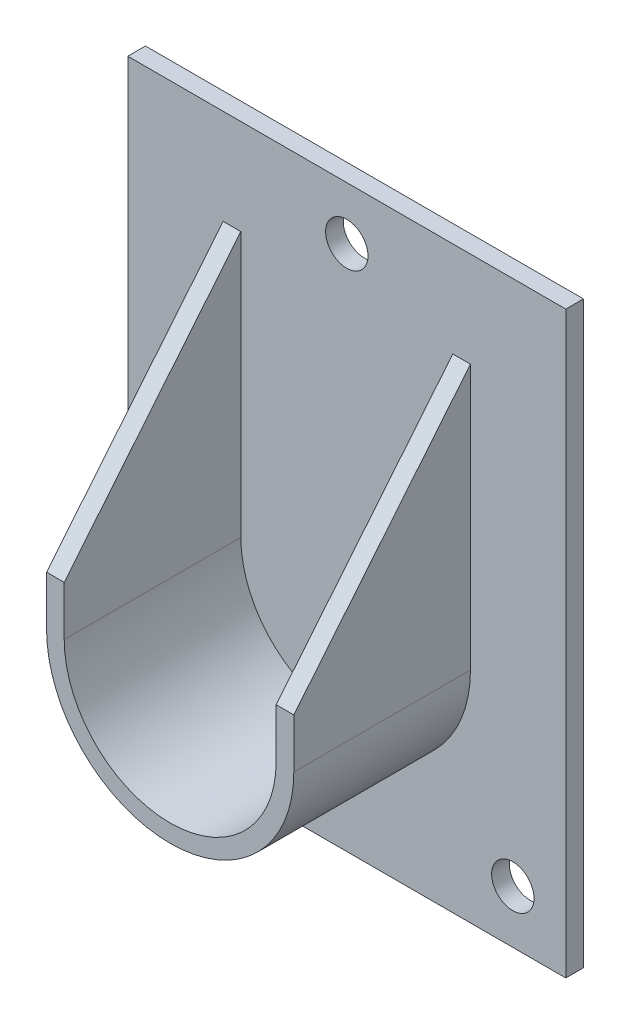
SolidWorks part; units mm, degrees
ref_plane "Front Plane" through (0, 0, 0) normal (0, 0, 1) x (1, 0, 0)
ref_plane "Top Plane" through (0, 0, 0) normal (0, 1, 0) x (1, 0, 0)
ref_plane "Right Plane" through (0, 0, 0) normal (1, 0, 0) x (0, 0, -1)
sketch "Sketch1" plane through (0, 0, 0) normal (0, 0, 1) x (1, 0, 0)
  line L0 (35, 75) -> (35, 0)
  line L1 (-62, 102) -> (62, 102)
  line L2 (-62, 102) -> (-62, -62)
  line L3 (-62, -62) -> (62, -62)
  line L4 (62, 102) -> (62, -62)
  line L5 (-35, 75) -> (-35, 0)
  line L6 (0, 19) -> (0, -35) construction
  line L7 (30, 75) -> (30, 0)
  line L8 (-30, 75) -> (-30, 0)
  line L9 (35, 75) -> (30, 75)
  line L10 (-30, 75) -> (-35, 75)
  circle A0 centre (0, 87) radius 6
  circle A1 centre (47, -47) radius 6
  arc A3 (-35, 0) -> (35, 0) centre (0, 0) ccw
  circle A4 centre (-47, -47) radius 6
  arc A5 (-30, 0) -> (30, 0) centre (0, 0) ccw
  point P4 (0, -62)
  dimension "D1" = 75
  dimension "D6" = 12
  dimension "D7" = 12
  dimension "D8" = 35
  dimension "D2" = 27
  dimension "D3" = 27
  dimension "D4" = 15
  dimension "D5" = 15
  dimension "D9" = 15
  dimension "D10" = 27
  dimension "D11" = 5
extrude "Boss-Extrude1" add sketch "Sketch1" along normal blind 5
extrude "Boss-Extrude2" add sketch "Sketch1<2>" along normal blind 55 contours A5 L6 A3 L0 L9 L7 | L6 A5 L8 L10 L5 A3 region at (33.8457, 37.5, 0) region at (-23.9325, -23.9325, 0)
sketch "Sketch1<2>" plane through (0, 0, 0) normal (0, 0, 1) x (1, 0, 0) same geometry as "Sketch1"
sketch "Sketch2" plane through (35, 0, 0) normal (1, 0, 0) x (0, 0, -1)
  line L0 (-5, 75) -> (-55, 14)
  line L1 (-55, 75) -> (-55, 0) construction
  line L2 (-55, 0) -> (-5, 0) construction
  line M3 (-5, 75) -> (-55, 75)
  line M4 (-55, 75) -> (-55, 0)
  dimension "D1" = 14
extrude "Cut-Extrude1" cut sketch "Sketch2" against normal through all and the other way through all contours L0 M3 M4 region at (35, 54.6667, 38.3333)
